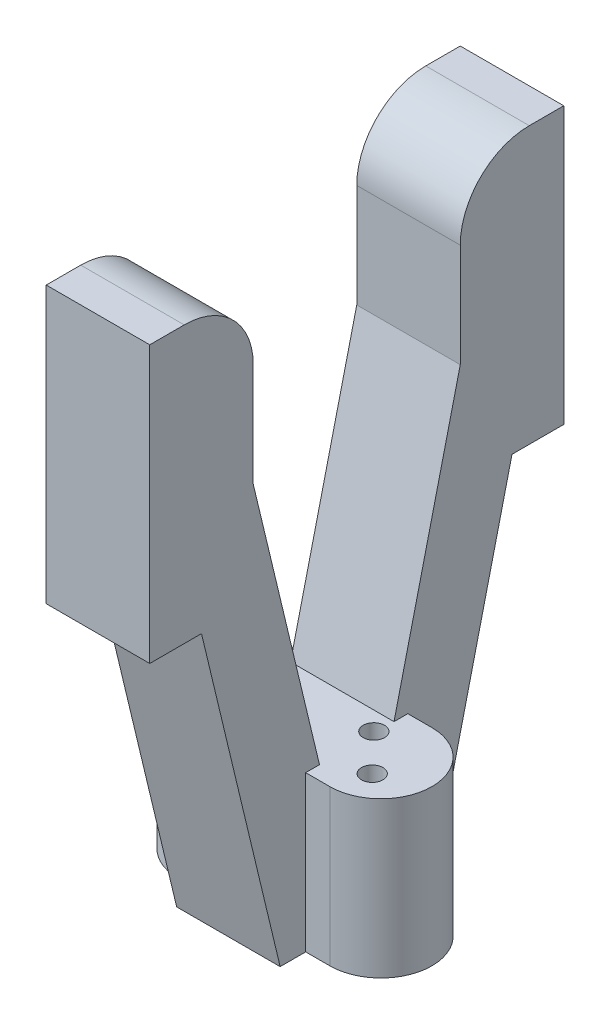
SolidWorks part; units mm, degrees
ref_plane "Front Plane" through (0, 0, 0) normal (0, 0, 1) x (1, 0, 0)
ref_plane "Top Plane" through (0, 0, 0) normal (0, 1, 0) x (1, 0, 0)
ref_plane "Right Plane" through (0, 0, 0) normal (1, 0, 0) x (0, 0, -1)
sketch "Sketch2" plane through (0, 0, 0) normal (1, 0, 0) x (0, 0, -1)
  line L0 (-6, 12.5) -> (-6, 9.5)
  line L1 (-6, 12.5) -> (0, 12.5) construction
  line L2 (-6, 9.5) -> (-4.5, 9.5)
  line L3 (-6, 12.5) -> (-3, 12.5) construction
  line L4 (-3, 12.5) -> (0, 0)
  line L5 (0, 0) -> (-2.22, 0)
  line L6 (-2.22, 0) -> (-4.5, 9.5)
  line L8 (-3, 17.5) -> (-6, 17.5)
  line L9 (-3, 17.5) -> (-3, 12.5)
  line L10 (-3, 12.5) -> (-6, 12.5) construction
  line L11 (-6, 17.5) -> (-6, 12.5)
  dimension "D1" = 6
  dimension "D2" = 3
  dimension "D3" = 1.5
  dimension "D4" = 3
  dimension "D5" = 12.5
  dimension "D6" = 5
extrude "Boss-Extrude2" add sketch "Sketch2" along normal blind 1.5 and the other way blind 1.5
sketch "Sketch1" plane through (0, 0, 0) normal (0, 1, 0) x (1, 0, 0)
  line L0 (-2.2, 0) -> (2.2, 0) construction
  line L1 (-2.2, 0) -> (2.2, 0) construction
  line L2 (-2.2, 1.48) -> (2.2, 1.48)
  line L3 (-2.2, -1.48) -> (2.2, -1.48)
  line L4 (0, 0) -> (0, -6) construction
  line L5 (1.4535, 0.542) -> (2.4904, -0.542) construction
  line L6 (1.972, 0) -> (-1.2108, 0) construction
  line L7 (1.972, 0) -> (2.9114, 0.8986) construction
  line L8 (1.972, 0) -> (0.3099, -1.5898) construction
  line L9 (-1.2108, 0) -> (0.3099, -1.5898) construction
  line L10 (-1.5, 0) -> (-1.5, -3) construction
  circle A0 centre (-2.2, 0) radius 0.63 construction
  circle A1 centre (2.2, 0) radius 0.63 construction
  arc A2 (-2.2, 1.48) -> (-2.2, -1.48) centre (-2.2, 0) ccw
  arc A3 (2.2, -1.48) -> (2.2, 1.48) centre (2.2, 0) ccw
  circle A4 centre (-1.2108, 0) radius 0.63
  circle A5 centre (1.4535, 0.542) radius 0.3104
  circle A6 centre (2.4904, -0.542) radius 0.3104
  point P4 (0, 0)
  point P7 (0, 0)
  dimension "D2" = 1.26
  dimension "D3" = 1.48
  dimension "D1" = 4.4
  dimension "D4" = 6
  dimension "D6" = 1.5
  dimension "D5" = 1.8099
  dimension "D7" = 3.6
  dimension "D8" = 1.3
  dimension "D9" = 2.2
extrude "Boss-Extrude3" add sketch "Sketch1" along normal blind 4.5 contours L3 A3 L2 A2
mirror "Mirror1" about plane through (0, 0, 0) normal (0, 0, 1) of "Boss-Extrude2"
extrude "Cut-Extrude2" cut sketch "Sketch1<3>" along normal through all contours A4 | A5 | A6 region at (-1.2108, 0, 0)
sketch "Sketch1<3>" plane through (0, 0, 0) normal (0, 1, 0) x (1, 0, 0) same geometry as "Sketch1"
fillet "Fillet1" radius 2 2 edges at (0, 17.5, -3) (0, 17.5, 3)
equation "\"TubingOD\"= 1.26"
equation "\"ConcentricDepth\"= 4.5mm"
equation "\"D2@Sketch1\"=\"TubingOD\""
equation "\"D1@Boss-Extrude3\"=\"ConcentricDepth\""
